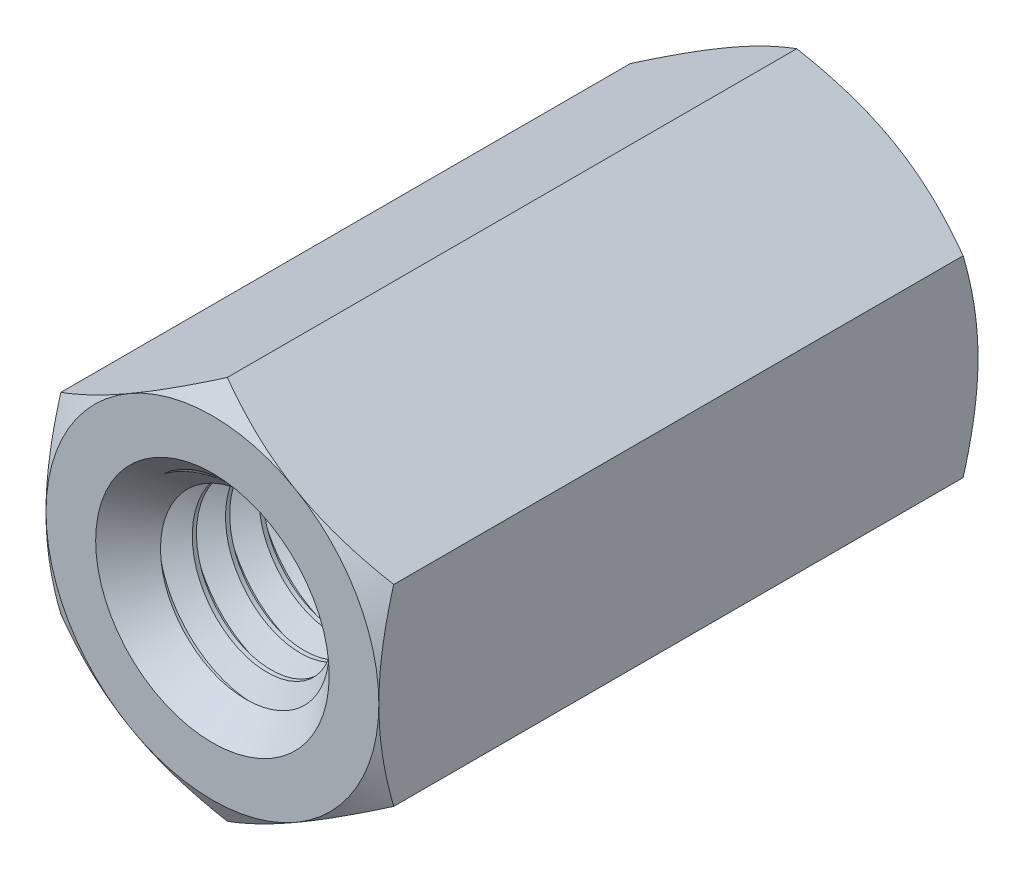
SolidWorks part; units mm, degrees
ref_plane "Front Plane" through (0, 0, 0) normal (0, 0, 1) x (1, 0, 0)
ref_plane "Top Plane" through (0, 0, 0) normal (0, 1, 0) x (1, 0, 0)
ref_plane "Right Plane" through (0, 0, 0) normal (1, 0, 0) x (0, 0, -1)
sketch "Sketch1" plane through (0, 0, 0) normal (0, 0, 1) x (1, 0, 0)
  line L1 (0, 2.8868) -> (-2.5, 1.4434)
  line L2 (-2.5, 1.4434) -> (-2.5, -1.4434)
  line L3 (-2.5, -1.4434) -> (0, -2.8868)
  line L4 (0, -2.8868) -> (2.5, -1.4434)
  line L5 (2.5, -1.4434) -> (2.5, 1.4434)
  line L6 (2.5, 1.4434) -> (0, 2.8868)
  circle A0 centre (0, 0) radius 2.5 construction
  dimension "Hex" = 5
extrude "Extrude1" add sketch "Sketch1" against normal blind 9
sketch "Sketch2" plane through (0, 0, 0) normal (0, 0, 1) x (1, 0, 0)
  circle A0 centre (0, 0) radius 2.5 construction
  circle A1 centre (0, 0) radius 2.5
extrude "Cut-Extrude1" cut sketch "Sketch2" against normal through all draft 60 flip side to cut
sketch "Sketch3" plane through (0, 0, -9) normal (0, 0, -1) x (-1, 0, 0)
  circle A1 centre (0, 0) radius 2.5
  circle A2 centre (0, 0) radius 2.5
  dimension "D1" = 0
extrude "Cut-Extrude2" cut sketch "Sketch3" against normal through all draft 60 flip side to cut
sketch "Sketch4" plane through (0, 0, 0) normal (0, 0, 1) x (1, 0, 0)
  circle A0 centre (0, 0) radius 1.5
  dimension "Thread Dia" = 3
extrude "Cut-Extrude3" cut sketch "Sketch4" against normal through all
sketch "Sketch7" plane through (0, 0, 0) normal (0, 0, 1) x (1, 0, 0)
  circle A4 centre (0, 0) radius 1.754
  circle A5 centre (0, 0) radius 1.754
  dimension "D1" = 0.254
sketch "Sketch8" plane through (0, 0, -9) normal (0, 0, -1) x (-1, 0, 0)
  circle A1 centre (0, 0) radius 1.754
  circle A2 centre (0, 0) radius 1.754 construction
sketch "Sketch5" plane through (0, 0, 0) normal (0, 0, 1) x (1, 0, 0)
  circle A0 centre (0, 0) radius 1.5 construction
  circle A1 centre (0, 0) radius 1.5
curve "Helix/Spiral1" pitch 0.5 height 9.5 radius 1.5 centre (0, 0, 0) axis (0, 0, -1) start towards (0, 1, 0) parameters "pitch"=0.5
sketch "Sketch9" plane through (0, 0, 0) normal (1, 0, 0) x (0, 0, -1)
  line L0 (-0.25, 1.5) -> (-0.1875, 1.5)
  line L1 (-0.1875, 1.5) -> (0, 1.1752)
  line L2 (-0.25, 1.5) -> (-0.4375, 1.1752)
  line L3 (-0.4375, 1.1752) -> (0, 1.1752)
  line L4 (-0.2187, 1.5) -> (-0.2187, 1.1752) construction
  line L5 (-0.3437, 1.3376) -> (-0.0937, 1.3376) construction
  line L7 (0, 1.1752) -> (0, 1.5) construction
  line L8 (0, 1.5) -> (0, -1.5) construction
  dimension "D1" = 0.0625
  dimension "D2" = 0.25
  dimension "D3" = 60
sketch "Sketch12" plane through (0, 0, 0) normal (0, 0, 1) x (1, 0, 0)
  circle A0 centre (0, 0) radius 1.1752
  circle A1 centre (0, 0) radius 1.5 construction
  circle A2 centre (0, 0) radius 1.5
extrude "Extrude2" add sketch "Sketch12" against normal up to surface (9 mm away) up to face at (1.5, 0, -9)
sweep "Cut-Sweep1" cut profiles "Sketch9" path "Helix/Spiral1"
extrude "Cut-Extrude6" cut sketch "Sketch7" against normal through all draft 45
extrude "Cut-Extrude7" cut sketch "Sketch8" against normal through all draft 45
equation "\"D2@Sketch9\" = \"pitch@Helix/Spiral1\"*.5"
equation "\"D3@Helix/Spiral1\" = \"pitch@Helix/Spiral1\"+\"Height@Extrude1\""
equation "\"D1@Sketch9\" = \"pitch@Helix/Spiral1\"*.125"
